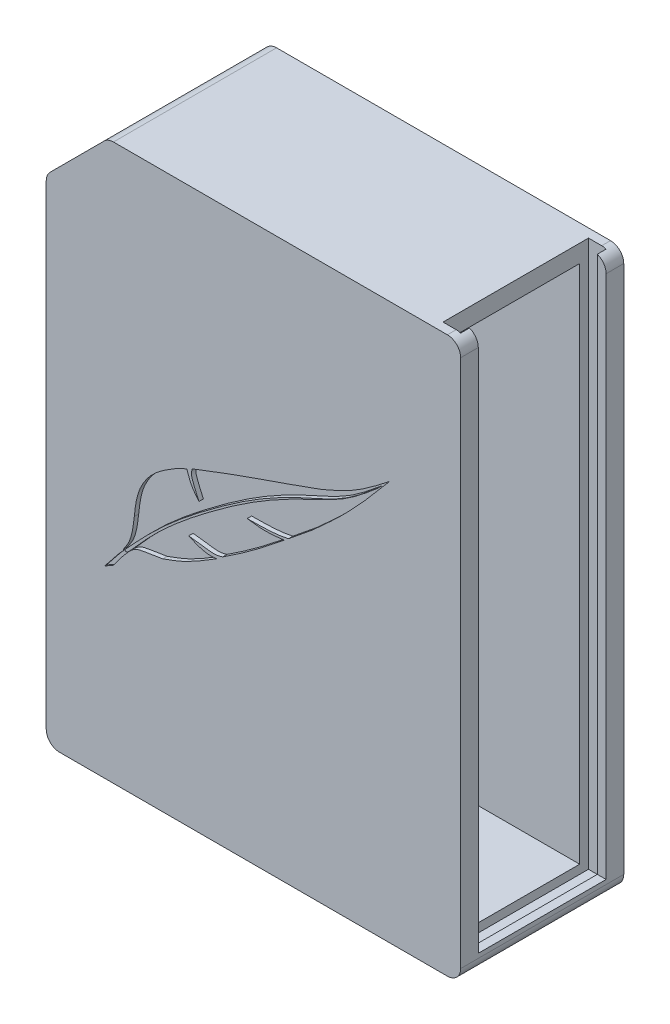
SolidWorks part; units mm, degrees
ref_plane "Plan de face" through (0, 0, 0) normal (0, 0, 1) x (1, 0, 0)
ref_plane "Plan de dessus" through (0, 0, 0) normal (0, 1, 0) x (1, 0, 0)
ref_plane "Plan de droite" through (0, 0, 0) normal (1, 0, 0) x (0, 0, -1)
sketch "Esquisse1" plane through (0, 0, 0) normal (0, 0, 1) x (1, 0, 0)
  line L0 (0, 56) -> (7, 63)
  line L1 (0, 0) -> (47, 0)
  line L2 (0, 0) -> (0, 63)
  line L3 (0, 63) -> (47, 63)
  line L4 (47, 0) -> (47, 63)
  dimension "D1" = 63
  dimension "D2" = 47
  dimension "D3" = 40
  dimension "D4" = 9.8995
extrude "Boss.-Extru.1" add sketch "Esquisse1" along normal blind 18.5 contours L1 L4 L3 L0 L2 region at (23.6766, 31.2567, 0)
sketch "Esquisse5" plane through (-28, 28, 0) normal (-0.7071, 0.7071, 0) x (0, 0, 1)
  line L1 (0, 49.4975) -> (18.5, 49.4975)
  line L2 (0, 49.4975) -> (0, 39.598)
  line L3 (0, 39.598) -> (18.5, 39.598)
  line L4 (18.5, 49.4975) -> (18.5, 39.598)
extrude "Boss.-Extru.3" add sketch "Esquisse5" against normal blind 1.5
fillet "Congé1" radius 1.5 5 edges at (0, 0, 9.25) (47, 0, 9.25) (47, 63, 9.25) (0, 56, 9.25) (7, 63, 9.25)
sketch "Esquisse7" plane through (0, 0, 18.5) normal (0, 0, 1) x (1, 0, 0)
  spline S0 degree 3 poles (8.7415, 23.5453) (8.9743, 23.8842) (9.3917, 24.492) (9.8012, 25.8095) (9.9123, 26.7617) (9.9858, 27.3915) knots 0 0 0 0 0.299076 0.53634 1 1 1 1
  spline S1 degree 3 poles (9.9858, 27.3915) (10.0834, 28.2789) (10.2851, 30.1136) (11.9307, 32.7943) (13.772, 33.9031) (14.7936, 34.5183) knots 0 0 0 0 0.294281 0.608472 1 1 1 1
  spline S2 degree 3 poles (14.7936, 34.5183) (14.9081, 34.5753) (15.1479, 34.6947) (15.5281, 34.8714) (15.7944, 34.9893) (15.9327, 35.0505) knots 0 0 0 0 0.30514 0.639136 1 1 1 1
  spline S3 degree 3 poles (15.9327, 35.0505) (15.9684, 34.9687) (16.1245, 34.6108) (16.393, 33.6755) (16.9532, 32.9886) (17.3202, 32.5386) knots 0 0 0 0 0.092718 0.405716 1 1 1 1
  spline S4 degree 3 poles (17.3202, 32.5386) (17.0956, 33.0342) (16.7405, 33.8181) (16.3988, 34.8154) (16.5293, 35.2467) (16.5656, 35.3667) knots 0 0 0 0 0.553685 0.875787 1 1 1 1
  spline S5 degree 3 poles (16.5656, 35.3667) (18.2245, 36.0048) (21.6822, 37.3348) (26.6151, 39.0046) (29.84, 40.172) (31.253, 40.6835) knots 0 0 0 0 0.341315 0.711412 1 1 1 1
  spline S6 degree 3 poles (31.253, 40.6835) (32.3248, 41.1433) (34.3078, 41.9939) (36.8262, 43.6575) (38.2748, 44.795) (38.9454, 45.3215) knots 0 0 0 0 0.387195 0.716321 1 1 1 1
  spline S7 degree 3 poles (38.9454, 45.3215) (38.4202, 44.6957) (36.7612, 42.7188) (33.9417, 39.5538) (31.4047, 37.265) (30.1783, 36.1586) knots 0 0 0 0 0.193087 0.609951 1 1 1 1
  spline S8 degree 3 poles (30.1783, 36.1586) (29.9757, 35.9982) (29.4625, 35.5922) (28.5696, 34.8494) (27.8698, 34.2787) (27.4769, 33.9583) knots 0 0 0 0 0.222488 0.563484 1 1 1 1
  spline S9 degree 3 poles (27.4769, 33.9583) (27.262, 33.9123) (26.5101, 33.7513) (24.9397, 33.622) (23.5892, 33.6048) (22.7874, 33.5946) knots 0 0 0 0 0.139881 0.489306 1 1 1 1
  spline S10 degree 3 poles (22.7874, 33.5946) (23.4704, 33.5009) (24.6788, 33.3349) (26.0923, 33.4724) (26.8132, 33.5569) (27.0097, 33.5799) knots 0 0 0 0 0.485971 0.859909 1 1 1 1
  spline S11 degree 3 poles (27.0097, 33.5799) (26.2925, 33.0079) (24.7977, 31.8159) (22.4783, 30.0696) (20.823, 28.9745) (19.9972, 28.4283) knots 0 0 0 0 0.316155 0.658882 1 1 1 1
  spline S12 degree 3 poles (19.9972, 28.4283) (19.7668, 28.3632) (19.1254, 28.1822) (17.82, 28.3885) (16.7763, 28.5078) (16.151, 28.5793) knots 0 0 0 0 0.183614 0.510917 1 1 1 1
  spline S13 degree 3 poles (16.151, 28.5793) (16.7065, 28.3354) (17.6096, 27.9388) (18.7309, 27.8272) (19.2255, 27.9021) (19.3462, 27.9204) knots 0 0 0 0 0.547076 0.889409 1 1 1 1
  spline S14 degree 3 poles (19.3462, 27.9204) (18.6495, 27.4904) (17.2958, 26.6548) (15.2594, 25.5862) (13.8711, 25.085) (13.2098, 24.8463) knots 0 0 0 0 0.357022 0.693778 1 1 1 1
  spline S15 degree 3 poles (13.2098, 24.8463) (12.5612, 24.7419) (11.57, 24.5823) (10.0743, 24.35) (9.4771, 23.765) (9.1374, 23.4322) knots 0 0 0 0 0.449394 0.686727 1 1 1 1
  spline S16 degree 3 poles (9.1374, 23.4322) (9.0951, 23.416) (8.9918, 23.3763) (8.8436, 23.4463) (8.77, 23.5177) (8.7415, 23.5453) knots 0 0 0 0 0.298494 0.728385 1 1 1 1
  spline S17 degree 3 poles (6.5356, 20.7597) (6.5893, 20.7895) (6.7647, 20.887) (7.0649, 21.0765) (7.3298, 21.2026) (7.4688, 21.2687) knots 0 0 0 0 0.173192 0.566196 1 1 1 1
  spline S18 degree 3 poles (7.4688, 21.2687) (7.5131, 21.3217) (7.6767, 21.5178) (7.9913, 21.9354) (8.2498, 22.3078) (8.4021, 22.5272) knots 0 0 0 0 0.132138 0.488781 1 1 1 1
  spline S19 degree 3 poles (8.4021, 22.5272) (9.7393, 24.0723) (12.766, 27.5694) (18.3602, 32.0846) (24.1478, 36.1439) (29.4393, 38.8797) (34.024, 40.9406) (36.3729, 42.9333) (37.5879, 43.9641) knots 0 0 0 0 0.167785 0.379771 0.589081 0.748039 0.86967 1 1 1 1
  spline S20 degree 3 poles (37.5879, 43.9641) (36.3225, 42.9123) (33.8569, 40.863) (29.1922, 38.9) (24.0683, 36.3127) (18.5521, 32.4553) (12.9478, 28.0102) (9.7057, 24.4772) (8.1759, 22.81) knots 0 0 0 0 0.134488 0.262039 0.413324 0.606279 0.814216 1 1 1 1
  spline S21 degree 3 poles (8.1759, 22.81) (8.0386, 22.6374) (7.6445, 22.1417) (7.0902, 21.4642) (6.6853, 20.9498) (6.5356, 20.7597) knots 0 0 0 0 0.252043 0.723507 1 1 1 1
extrude "Enlèv. mat.-Extru.7" cut sketch "Esquisse7" against normal blind 0.5 contours S20 S19 S15 S14 S13 S12 S11 S10 S9 S8 S7 S6 S5 S4 S3 S2 S1 S0 S16 region at (20.7244, 33.0885, 18.5)
sketch "Esquisse8" plane through (0, 0, 18.5) normal (0, 0, 1) x (1, 0, 0)
  spline S0 degree 3 poles (8.8233, 23.6324) (9.0561, 23.9713) (9.4735, 24.5791) (9.883, 25.8966) (9.9941, 26.8488) (10.0676, 27.4786) knots 0 0 0 0 0.299076 0.53634 1 1 1 1
  spline S1 degree 3 poles (10.0676, 27.4786) (10.1652, 28.3659) (10.3669, 30.2007) (12.0125, 32.8814) (13.8538, 33.9902) (14.8754, 34.6054) knots 0 0 0 0 0.294281 0.608472 1 1 1 1
  spline S2 degree 3 poles (14.8754, 34.6054) (14.9899, 34.6624) (15.2297, 34.7818) (15.6099, 34.9585) (15.8762, 35.0764) (16.0145, 35.1376) knots 0 0 0 0 0.30514 0.639136 1 1 1 1
  spline S3 degree 3 poles (16.0145, 35.1376) (16.0502, 35.0558) (16.2063, 34.6979) (16.4748, 33.7626) (17.035, 33.0757) (17.402, 32.6257) knots 0 0 0 0 0.092718 0.405716 1 1 1 1
  spline S4 degree 3 poles (17.402, 32.6257) (17.1774, 33.1213) (16.8223, 33.9052) (16.4806, 34.9025) (16.6111, 35.3338) (16.6474, 35.4538) knots 0 0 0 0 0.553685 0.875787 1 1 1 1
  spline S5 degree 3 poles (16.6474, 35.4538) (18.3063, 36.0919) (21.764, 37.4219) (26.6969, 39.0917) (29.9218, 40.2591) (31.3348, 40.7706) knots 0 0 0 0 0.341315 0.711412 1 1 1 1
  spline S6 degree 3 poles (31.3348, 40.7706) (32.4066, 41.2303) (34.3896, 42.0809) (36.908, 43.7446) (38.3566, 44.8821) (39.0271, 45.4086) knots 0 0 0 0 0.387195 0.716321 1 1 1 1
  spline S7 degree 3 poles (39.0271, 45.4086) (38.502, 44.7828) (36.843, 42.8058) (34.0235, 39.6409) (31.4865, 37.352) (30.2601, 36.2456) knots 0 0 0 0 0.193087 0.609951 1 1 1 1
  spline S8 degree 3 poles (30.2601, 36.2456) (30.0575, 36.0853) (29.5443, 35.6792) (28.6514, 34.9365) (27.9516, 34.3658) (27.5587, 34.0454) knots 0 0 0 0 0.222488 0.563484 1 1 1 1
  spline S9 degree 3 poles (27.5587, 34.0454) (27.3438, 33.9994) (26.5919, 33.8383) (25.0215, 33.7091) (23.671, 33.6919) (22.8692, 33.6817) knots 0 0 0 0 0.139881 0.489306 1 1 1 1
  spline S10 degree 3 poles (22.8692, 33.6817) (23.5522, 33.5879) (24.7606, 33.422) (26.1741, 33.5594) (26.895, 33.644) (27.0915, 33.667) knots 0 0 0 0 0.485971 0.859909 1 1 1 1
  spline S11 degree 3 poles (27.0915, 33.667) (26.3743, 33.095) (24.8795, 31.903) (22.5601, 30.1567) (20.9048, 29.0616) (20.079, 28.5154) knots 0 0 0 0 0.316155 0.658882 1 1 1 1
  spline S12 degree 3 poles (20.079, 28.5154) (19.8486, 28.4503) (19.2072, 28.2693) (17.9018, 28.4756) (16.8581, 28.5949) (16.2328, 28.6664) knots 0 0 0 0 0.183614 0.510917 1 1 1 1
  spline S13 degree 3 poles (16.2328, 28.6664) (16.7883, 28.4225) (17.6913, 28.0259) (18.8127, 27.9143) (19.3072, 27.9892) (19.428, 28.0075) knots 0 0 0 0 0.547076 0.889409 1 1 1 1
  spline S14 degree 3 poles (19.428, 28.0075) (18.7313, 27.5774) (17.3775, 26.7418) (15.3412, 25.6733) (13.9529, 25.172) (13.2916, 24.9333) knots 0 0 0 0 0.357022 0.693778 1 1 1 1
  spline S15 degree 3 poles (13.2916, 24.9333) (12.643, 24.8289) (11.6518, 24.6694) (10.1561, 24.4371) (9.5589, 23.8521) (9.2192, 23.5193) knots 0 0 0 0 0.449394 0.686727 1 1 1 1
  spline S16 degree 3 poles (9.2192, 23.5193) (9.1769, 23.503) (9.0735, 23.4634) (8.9254, 23.5333) (8.8518, 23.6048) (8.8233, 23.6324) knots 0 0 0 0 0.298494 0.728385 1 1 1 1
  spline S17 degree 3 poles (6.6174, 20.8468) (6.6711, 20.8766) (6.8465, 20.9741) (7.1467, 21.1636) (7.4116, 21.2897) (7.5506, 21.3558) knots 0 0 0 0 0.173192 0.566196 1 1 1 1
  spline S18 degree 3 poles (7.5506, 21.3558) (7.5949, 21.4088) (7.7585, 21.6049) (8.073, 22.0224) (8.3316, 22.3949) (8.4839, 22.6143) knots 0 0 0 0 0.132138 0.488781 1 1 1 1
  spline S19 degree 3 poles (8.4839, 22.6143) (9.8211, 24.1594) (12.8478, 27.6565) (18.4419, 32.1717) (24.2296, 36.231) (29.5211, 38.9668) (34.1058, 41.0277) (36.4547, 43.0204) (37.6697, 44.0511) knots 0 0 0 0 0.167785 0.379771 0.589081 0.748039 0.86967 1 1 1 1
  spline S20 degree 3 poles (37.6697, 44.0511) (36.4042, 42.9994) (33.9387, 40.9501) (29.274, 38.9871) (24.15, 36.3998) (18.6339, 32.5424) (13.0296, 28.0973) (9.7875, 24.5642) (8.2577, 22.8971) knots 0 0 0 0 0.134488 0.262039 0.413324 0.606279 0.814216 1 1 1 1
  spline S21 degree 3 poles (8.2577, 22.8971) (8.1204, 22.7244) (7.7263, 22.2287) (7.172, 21.5513) (6.7671, 21.0369) (6.6174, 20.8468) knots 0 0 0 0 0.252043 0.723507 1 1 1 1
  spline M74 degree 3 poles (37.5879, 43.9641) (36.3225, 42.9123) (33.8569, 40.863) (29.1922, 38.9) (24.0683, 36.3127) (18.5521, 32.4553) (12.9478, 28.0102) (9.7057, 24.4772) (8.1759, 22.81) knots 0 0 0 0 0.134488 0.262039 0.413324 0.606279 0.814216 1 1 1 1 only from (37.5879, 43.9641) to (8.8007, 23.4903)
  spline M75 degree 3 poles (9.1374, 23.4322) (9.0951, 23.416) (8.9918, 23.3763) (8.8436, 23.4463) (8.77, 23.5177) (8.7415, 23.5453) knots 0 0 0 0 0.298494 0.728385 1 1 1 1 only from (8.8007, 23.4903) to (8.7415, 23.5453)
extrude "Enlèv. mat.-Extru.9" cut sketch "Esquisse8" against normal blind 0.2 contours S20 S21 S17 S18 S19 S15 S16 M74 M75 region at (8.0046, 22.2756, 18.5)
sketch "Esquisse10" plane through (0, 0, 0) normal (0, 0, -1) x (-1, 0, 0)
  line L0 (-47.6009, 61) -> (-7.8284, 61)
  line L1 (-7.8284, 61) -> (-2, 55.1716)
  line L2 (-2, 55.1716) -> (-2, 2)
  line L3 (-2, 2) -> (-47.6009, 2)
  line L4 (-47.6009, 2) -> (-47.6009, 61)
  line L5 (-7.6213, 63) -> (-45.5, 63) construction
  line L6 (-1.5, 0) -> (-45.5, 0) construction
  line L7 (0, 1.5) -> (0, 55.3787) construction
  line L10 (-0.4393, 56.4393) -> (-6.5607, 62.5607) construction
  point P11 (-3.5, 59.5)
  dimension "D1" = 2
  dimension "D2" = 2
  dimension "D3" = 2
  dimension "D4" = 2
  dimension "D5" = 2
  dimension "D6" = 59
extrude "Enlèv. mat.-Extru.10" cut sketch "Esquisse10" along direction (0, 0, 1) on the side against the normal blind 14.5 from offset 2 offset against normal yes
sketch "Esquisse11" plane through (0, 0, 2) normal (0, 0, 1) x (1, 0, 0)
  line L0 (47, 2) -> (47, 61) construction
  line L1 (44, 67.4505) -> (46, 67.4505)
  line L2 (44, 67.4505) -> (44, 1)
  line L3 (44, 1) -> (46, 1)
  line L4 (46, 67.4505) -> (46, 1)
  line L6 (1.5, 0) -> (45.5, 0) construction
  dimension "D1" = 2
  dimension "D2" = 1
  dimension "D3" = 1
extrude "Enlèv. mat.-Extru.11" cut sketch "Esquisse11" against normal blind 1 and the other way blind 15.5
sketch "Esquisse12" plane through (0, 0, 2) normal (0, 0, 1) x (1, 0, 0)
  line L0 (46, 61) -> (46, 2) construction
  line L1 (46, 59.7876) -> (48.4775, 59.7876)
  line L2 (46, 59.7876) -> (46, 63.7473)
  line L3 (46, 63.7473) -> (48.4775, 63.7473)
  line L4 (48.4775, 59.7876) -> (48.4775, 63.7473)
extrude "Enlèv. mat.-Extru.12" cut sketch "Esquisse12" along normal blind 14.5
sketch "Esquisse13" plane through (0, 0, 2) normal (0, 0, 1) x (1, 0, 0)
  line L0 (0, 1.5) -> (0, 55.3787) construction
  line L1 (0, 45.8) -> (2, 45.8)
  line L2 (0, 45.8) -> (0, 36.8)
  line L3 (0, 36.8) -> (2, 36.8)
  line L4 (2, 45.8) -> (2, 36.8)
  line L5 (2, 2) -> (2, 55.1716) construction
  line L6 (44, 2) -> (2, 2) construction
  dimension "D1" = 9
  dimension "D2" = 34.8
extrude "Enlèv. mat.-Extru.13" cut sketch "Esquisse13" along normal blind 2 from offset 3
